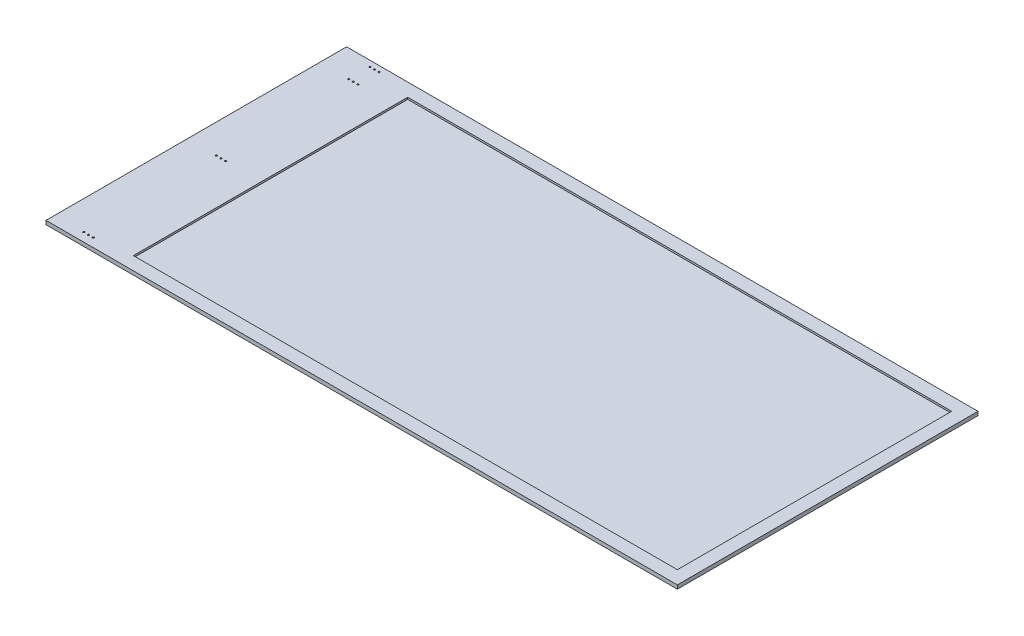
SolidWorks part; units mm, degrees
material "Pine"
ref_plane "Front Plane" through (0, 0, 0) normal (0, 0, 1) x (1, 0, 0)
ref_plane "Top Plane" through (0, 0, 0) normal (0, 1, 0) x (1, 0, 0)
ref_plane "Right Plane" through (0, 0, 0) normal (1, 0, 0) x (0, 0, -1)
sketch "Sketch1" plane through (0, 0, 0) normal (0, 1, 0) x (1, 0, 0)
  line L1 (0, 0) -> (1066.8, 0)
  line L2 (0, 0) -> (0, 508)
  line L3 (0, 508) -> (1066.8, 508)
  line L4 (1066.8, 0) -> (1066.8, 508)
  dimension "D1" = 1066.8
  dimension "D2" = 508
extrude "Boss-Extrude1" add sketch "Sketch1" along normal blind 6.35
sketch "Sketch2" plane through (0, 6.35, 0) normal (0, 1, 0) x (1, 0, 0)
  line L1 (125.4125, 485.775) -> (1044.575, 485.775)
  line L2 (125.4125, 485.775) -> (125.4125, 22.225)
  line L3 (125.4125, 22.225) -> (1044.575, 22.225)
  line L4 (1044.575, 485.775) -> (1044.575, 22.225)
  line L5 (0, 254) -> (1066.8, 254) construction
  line L6 (0, 508) -> (0, 0) construction
  line L7 (1066.8, 0) -> (1066.8, 508) construction
  point P10 (125.4125, 254)
  dimension "D1" = 919.1625
  dimension "D2" = 463.55
  dimension "D3" = 22.225
extrude "Cut-Extrude1" cut sketch "Sketch2" against normal blind 3.175
sketch "Sketch3" plane through (0, 6.35, 0) normal (0, 1, 0) x (1, 0, 0)
  line L0 (49.149, 462.4832) -> (49.149, -139.6835) construction
  line L1 (1044.575, 22.225) -> (1044.575, 485.775) construction
  line L2 (0, 508) -> (0, 0) construction
  line L3 (49.149, 498.094) -> (49.149, 508) construction
  line L4 (1066.8, 508) -> (0, 508) construction
  line L5 (1066.8, 0) -> (1066.8, 508) construction
  circle A0 centre (49.149, 462.4832) radius 1.3589
  circle A1 centre (49.149, 498.094) radius 1.3589
  circle A2 centre (56.8452, 498.094) radius 1.3589
  circle A3 centre (56.8452, 462.4832) radius 1.3589
  circle A4 centre (64.5414, 498.094) radius 1.3589
  circle A5 centre (64.5414, 462.4832) radius 1.3589
  circle A9 centre (49.149, 14.8082) radius 1.3589
  circle A10 centre (57.0992, 14.8082) radius 1.3589
  circle A11 centre (65.0494, 14.8082) radius 1.3589
  circle A12 centre (49.149, 238.6457) radius 1.3589
  circle A13 centre (57.0992, 238.6457) radius 1.3589
  circle A14 centre (65.0494, 238.6457) radius 1.3589
  dimension "D2" = 2.7178
  dimension "D3" = 2.7178
  dimension "D9" = 2.7178
  dimension "D5" = 9.906
  dimension "D1" = 35.6108
  dimension "D6" = 995.426
  dimension "D7" = 7.6962
  dimension "D8" = 49.149
  dimension "D10" = 447.675
  dimension "D11" = 7.9502
  dimension "D13" = 223.8375
  dimension "D4" = 3
  dimension "D12" = 3
extrude "Cut-Extrude2" cut sketch "Sketch3" against normal through all
